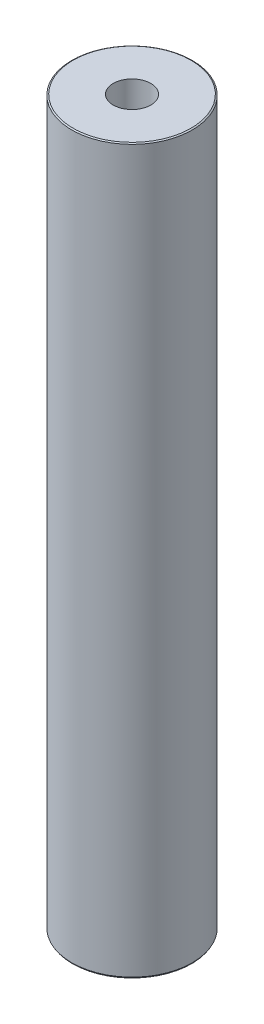
SolidWorks part; units mm, degrees
ref_plane "Front Plane" through (0, 0, 0) normal (0, 0, 1) x (1, 0, 0)
ref_plane "Top Plane" through (0, 0, 0) normal (0, 1, 0) x (1, 0, 0)
ref_plane "Right Plane" through (0, 0, 0) normal (1, 0, 0) x (0, 0, -1)
sketch "Sketch1" plane through (0, 0, 0) normal (0, 1, 0) x (1, 0, 0)
  circle A0 centre (0, 0) radius 50
  dimension "SHAFT_OD" = 100
extrude "Boss-Extrude1" add sketch "Sketch1" along normal blind 600
sketch "Sketch2" plane through (0, 0, 0) normal (0, 1, 0) x (1, 0, 0)
  circle A0 centre (0, 0) radius 15.5864
  dimension "BORE_D" = 31.1728
extrude "Cut-Extrude1" cut sketch "Sketch2" along normal through all
chamfer "Chamfer1" distance 0.6711 angle 58.551 2 edges at (0, 600, 50) (0, 0, 50) first distance on face at (0, 600, 50) first distance on face at (0, 0, 15.5864)
